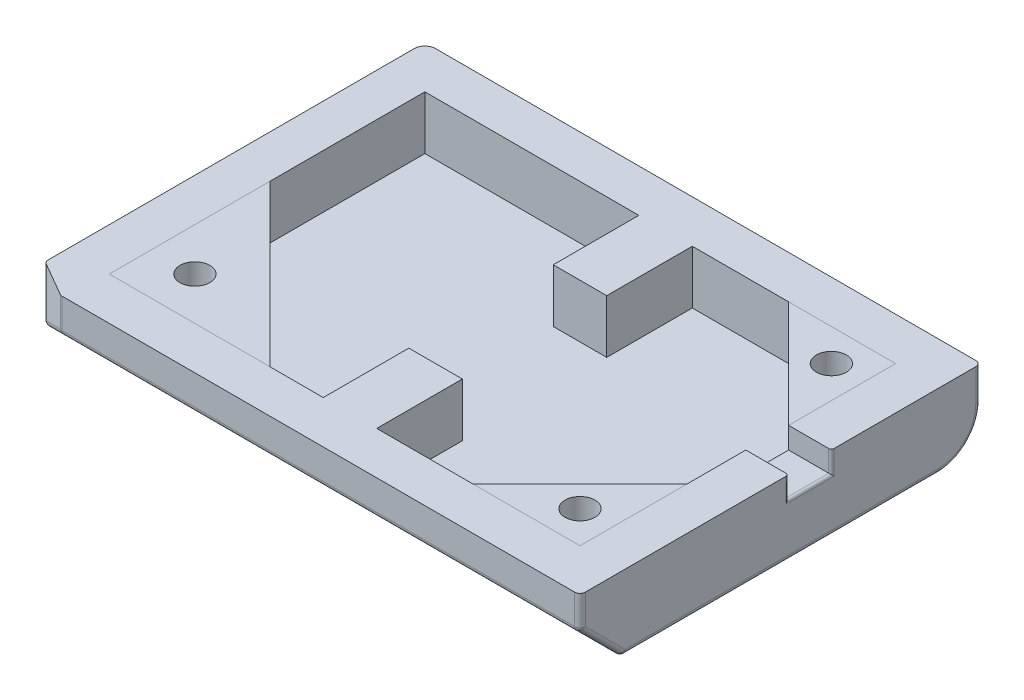
SolidWorks part; units mm, degrees
ref_plane "Спереди" through (0, 0, 0) normal (0, 0, 1) x (1, 0, 0)
ref_plane "Сверху" through (0, 0, 0) normal (0, 1, 0) x (1, 0, 0)
ref_plane "Справа" through (0, 0, 0) normal (1, 0, 0) x (0, 0, -1)
sketch "Эскиз1" plane through (0, 0, 0) normal (0, 1, 0) x (1, 0, 0)
  line L0 (-26, 18.75) -> (26, 18.75)
  line L2 (-26, 18.75) -> (-26, -18.75)
  line L3 (-26, -18.75) -> (26, -18.75)
  line L4 (26, -18.75) -> (26, 18.75)
extrude "Бобышка-Вытянуть1" add sketch "Эскиз1" along normal blind 7
chamfer "Фаска1" distance 4 angle 45 1 edges at (0, 0, 18.75)
fillet "Скругление1" radius 4 1 edges at (0, 0, -18.75)
ref_plane "Плоскость4" through (0, 7, 0) normal (0, 1, 0) x (1, 0, 0)
sketch "Эскиз2" plane through (0, 7, 0) normal (0, 1, 0) x (1, 0, 0)
  line L3 (-22, 14.75) -> (22, 14.75)
  line L4 (22, 14.75) -> (22, -14.75)
  line L5 (22, -14.75) -> (-22, -14.75)
  line L6 (-22, -14.75) -> (-22, 14.75)
extrude "Вырез-Вытянуть1" cut sketch "Эскиз2" against normal blind 5
sketch "Эскиз3" plane through (0, 7, 0) normal (0, 1, 0) x (1, 0, 0)
  line L2 (22, -14.75) -> (22, 14.75) construction
  line L3 (22, 4.75) -> (26, 4.75)
  line L4 (26, -18.75) -> (26, 18.75) construction
  line L5 (26, 4.75) -> (26, 0.75)
  line L6 (26, 0.75) -> (22, 0.75)
  line L7 (22, 0.75) -> (22, 4.75)
extrude "Вырез-Вытянуть2" cut sketch "Эскиз3" against normal blind 2
sketch "Эскиз4" plane through (0, 7, 0) normal (0, 1, 0) x (1, 0, 0)
  line L1 (22, 14.75) -> (-22, 14.75) construction
  line L2 (-2, 14.75) -> (-2, -14.75)
  line L3 (-22, -14.75) -> (22, -14.75) construction
  line L4 (-2, -14.75) -> (3, -14.75)
  line L5 (3, -14.75) -> (3, 14.75)
  line L6 (3, 14.75) -> (-2, 14.75)
extrude "Бобышка-Вытянуть2" add sketch "Эскиз4" against normal blind 5
sketch "Эскиз5" plane through (0, 7, 0) normal (0, 1, 0) x (1, 0, 0)
  line L1 (-2, 14.75) -> (-2, -14.75) construction
  line L3 (-2, -6.75) -> (-2, 6.75)
  line L4 (-2, 6.75) -> (3, 6.75)
  line L5 (3, -14.75) -> (3, 14.75) construction
  line L6 (3, 6.75) -> (3, -6.75)
  line L7 (3, -6.75) -> (-2, -6.75)
extrude "Вырез-Вытянуть3" cut sketch "Эскиз5" against normal blind 5
fillet "Скругление2" radius 1 3 edges at (-26, 0, 0) (-26, 1.1716, -17.5784) (-26, 5.5, -18.75)
chamfer "Фаска2" distance 2 angle 60 1 edges at (-26, 5.5, 18.75) first distance on face at (-26, 3.8964, 0.3964)
sketch "Эскиз6" plane through (0, 7, 0) normal (0, 1, 0) x (1, 0, 0)
  line L1 (-22, 14.75) -> (-22, -14.75) construction
  line L2 (-22, -14.75) -> (-7, -14.75)
  line L3 (-22, -14.75) -> (-2, -14.75) construction
  line L4 (-7, -14.75) -> (-22, 0.25)
  line L5 (-22, -14.75) -> (-22, 0.25)
  line L6 (22, 4.75) -> (22, 14.75)
  line L8 (22, 14.75) -> (3, 14.75) construction
  line L9 (12, 14.75) -> (22, 4.75)
  line L10 (12, 14.75) -> (22, 14.75)
  line L12 (22, -14.75) -> (22, 0.75) construction
  line L13 (22, -14.75) -> (12, -14.75)
  line L14 (3, -14.75) -> (22, -14.75) construction
  line L15 (12, -14.75) -> (22, -4.75)
  line L16 (22, -4.75) -> (22, -14.75)
  circle A0 centre (-18, -10.75) radius 1.4
  circle A1 centre (19, 11.75) radius 1.4
  circle A2 centre (19, -11.75) radius 1.4
extrude "Бобышка-Вытянуть4" add sketch "Эскиз6" against normal blind 5 separate body
fillet "Скругление3" radius 0.5 12 edges at (26, 0, 0) (26, 5.5, -18.75) (-26, 1.5, 16.25) (-25.7071, 0.2929, 15.0429) (-22.5359, 5.5, 18.75) (-26, 4.5, 16.75) (-24.2679, 3, 17.75) (26, 1.1716, -17.5784) (0.5, 0, 14.75) (1.7321, 4, 18.75) (26, 2, 16.75) (26, 5.5, 18.75)
fillet "Скругление4" radius 0.25 3 edges at (26, 6, -4.75) (26, 6, -0.75) (26, 5, -2.75)
